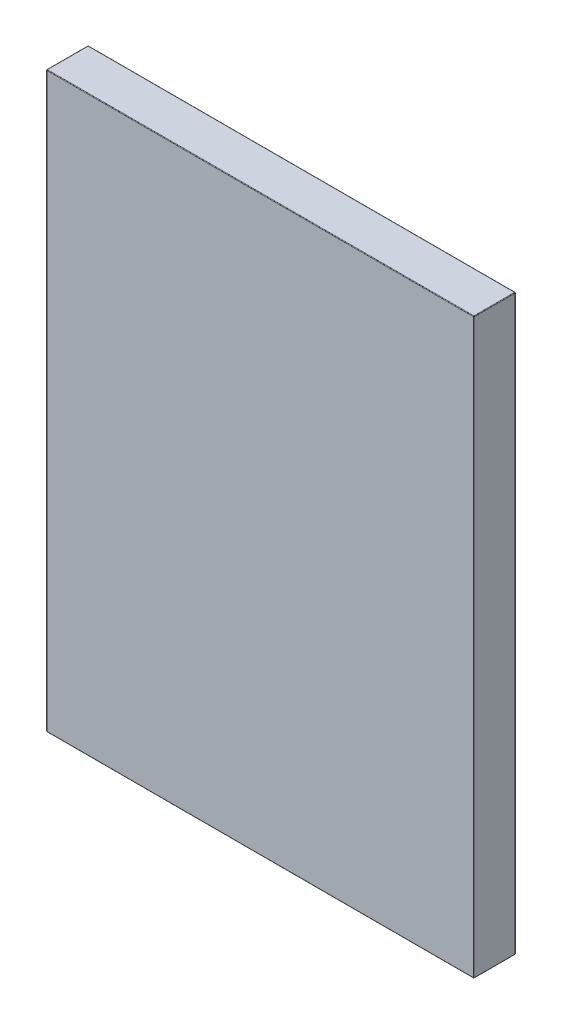
SolidWorks part; units mm, degrees
material "C (Графит)"
ref_plane "Front" through (0, 0, 0) normal (0, 0, 1) x (1, 0, 0)
ref_plane "Top" through (0, 0, 0) normal (0, 1, 0) x (1, 0, 0)
ref_plane "Right" through (0, 0, 0) normal (1, 0, 0) x (0, 0, -1)
sketch "Эскиз1" plane through (0, 0, 0) normal (0, 0, 1) x (1, 0, 0)
  line L1 (-410, 550) -> (410, 550)
  line L2 (-410, 550) -> (-410, -550)
  line L3 (-410, -550) -> (410, -550)
  line L4 (410, 550) -> (410, -550)
  line L5 (-410, 550) -> (410, -550) construction
  line L6 (-410, -550) -> (410, 550) construction
  point P0 (0, 0)
  dimension "D1" = 820
  dimension "D2" = 1100
extrude "Бобышка-Вытянуть1" add sketch "Эскиз1" along normal blind 80
fillet "Скругление1" radius 1 4 edges at (0, 550, 0) (-410, 0, 0) (0, -550, 0) (410, 0, 0)
fillet "Скругление2" radius 1 12 edges at (409.7071, -549.7071, 0.2929) (-409.7071, -549.7071, 0.2929) (-409.7071, 549.7071, 0.2929) (409.7071, 549.7071, 0.2929) (410, -550, 40.5) (-410, -550, 40.5) (-410, 550, 40.5) (410, 550, 40.5) (0, -550, 80) (-410, 0, 80) (0, 550, 80) (410, 0, 80)
